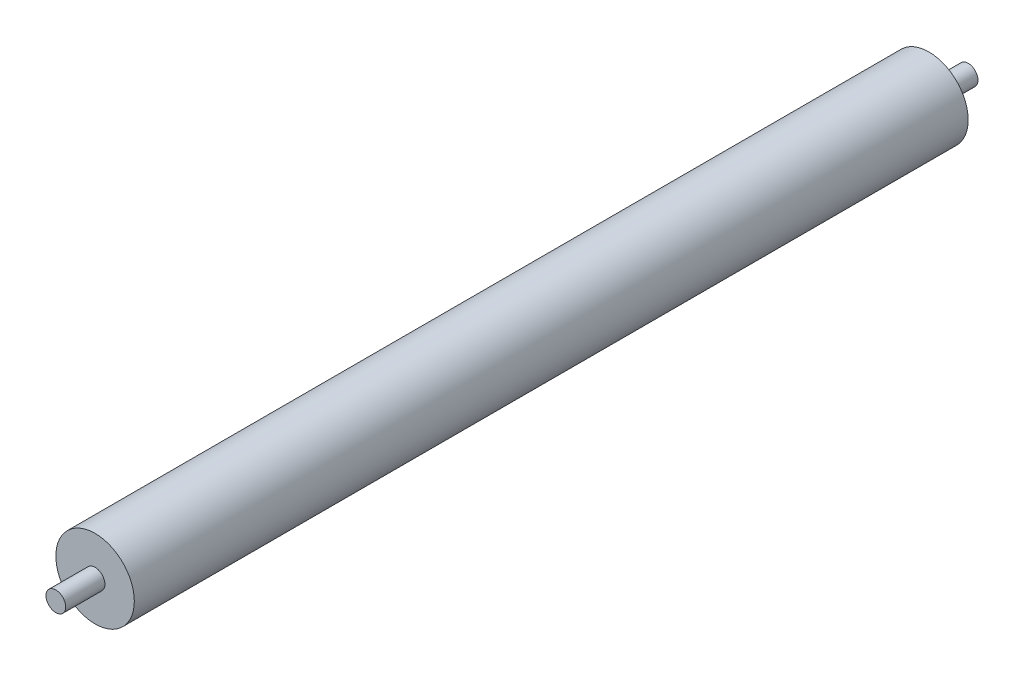
SolidWorks part; units mm, degrees
material "Polyurethane Foam Flexible"
ref_plane "Front Plane" through (0, 0, 0) normal (0, 0, 1) x (1, 0, 0)
ref_plane "Top Plane" through (0, 0, 0) normal (0, 1, 0) x (1, 0, 0)
ref_plane "Right Plane" through (0, 0, 0) normal (1, 0, 0) x (0, 0, -1)
sketch "Sketch1" plane through (0, 0, 0) normal (0, 0, 1) x (1, 0, 0)
  circle A0 centre (0, 0) radius 25.4
extrude "Boss-Extrude1" add sketch "Sketch1" along normal blind 590.55 contours A0
sketch "Sketch2" plane through (0, 0, 0) normal (0, 0, 1) x (1, 0, 0)
  circle A0 centre (0, 0) radius 6.3619
extrude "Cut-Extrude1" cut sketch "Sketch2" along normal blind 25.4 flip side to cut contours A0
sketch "Sketch5" plane through (0, 0, 590.55) normal (0, 0, 1) x (1, 0, 0)
  circle A0 centre (0, 0) radius 6.3779
extrude "Cut-Extrude4" cut sketch "Sketch5" against normal blind 25.4 flip side to cut
